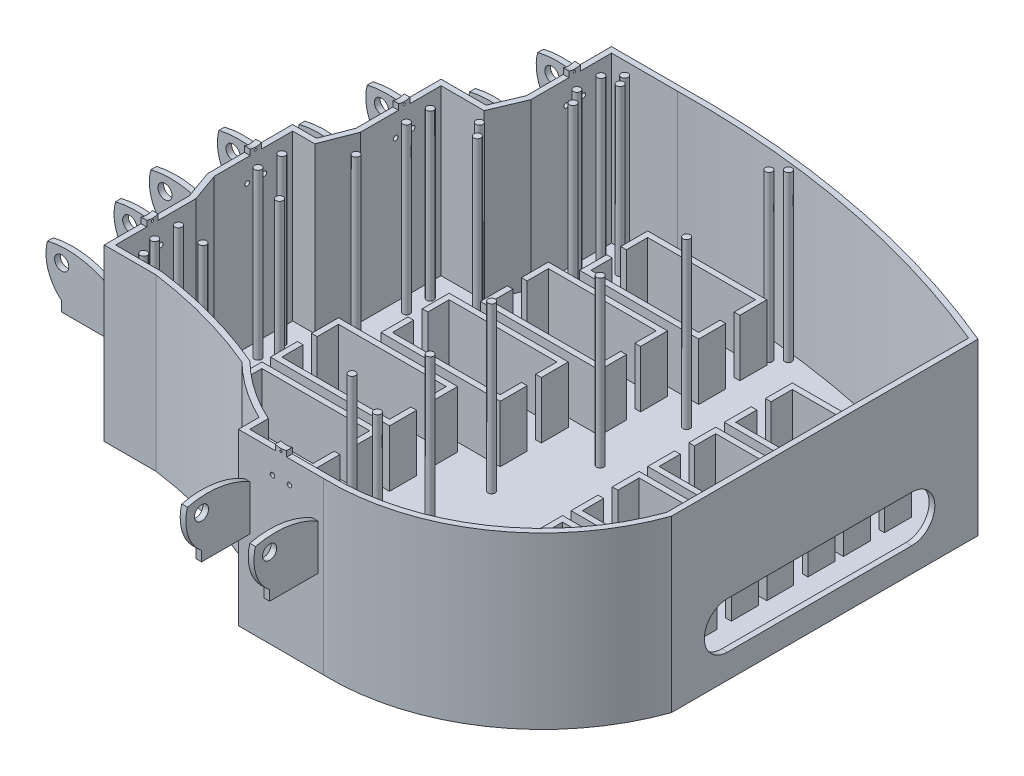
SolidWorks part; units mm, degrees
ref_plane "Front Plane" through (0, 0, 0) normal (0, 0, 1) x (1, 0, 0)
ref_plane "Top Plane" through (0, 0, 0) normal (0, 1, 0) x (1, 0, 0)
ref_plane "Right Plane" through (0, 0, 0) normal (1, 0, 0) x (0, 0, -1)
ref_plane "Palm Side Plane" through (0, 38.1, 0) normal (0, 1, 0) x (1, 0, 0)
ref_plane "Left Side Plane" through (0, 0, 63.5) normal (0, 0, 1) x (1, 0, 0)
ref_plane "Top Side Plane" through (-69.85, 0, 0) normal (1, 0, 0) x (0, 0, -1)
ref_plane "Wrist Plane" through (62.9138, 0, 0) normal (1, 0, 0) x (0, 0, -1)
sketch "Hand Direction Arrow" plane through (0, 38.1, 0) normal (0, 1, 0) x (1, 0, 0)
  line L0 (49.8191, -114.0829) -> (-36.738, -114.0829) construction
  line L1 (-36.738, -114.0829) -> (-22.4792, -131.555) construction
  line L2 (-36.738, -114.0829) -> (-22.4792, -99.8241) construction
sketch "Sketch2" plane through (0, 0, 0) normal (0, 1, 0) x (1, 0, 0)
  line L5 (-69.85, -63.5) -> (69.85, 63.5) construction
  line L6 (-69.85, 63.5) -> (69.85, -63.5) construction
  line L7 (-20.7784, 52.7587) -> (-36.189, 52.7587)
  line L8 (-36.189, 52.7587) -> (-36.189, 33.7087)
  line L9 (-42.9594, -42.4913) -> (-54.5039, -42.4913)
  line L10 (-54.5039, -42.4913) -> (-54.5039, -23.4413)
  line L11 (-54.5039, -23.4413) -> (-56.7676, -17.0913)
  line L12 (-51.4171, 1.9587) -> (-48.9477, 8.3087)
  line L14 (-56.7676, -17.0913) -> (-56.7676, 1.9587)
  line L15 (-56.7676, 1.9587) -> (-51.4171, 1.9587)
  line L16 (-38.8642, 27.3587) -> (-36.189, 33.7087)
  line L19 (15.3118, -63.2103) -> (-3.7382, -63.2103)
  line L20 (-3.7382, -63.2103) -> (-3.7382, -58.593)
  line L21 (61.5724, -31.5884) -> (61.5724, 37.0553)
  line L22 (-48.9477, 8.3087) -> (-48.9477, 27.3587)
  line L23 (-48.9477, 27.3587) -> (-38.8642, 27.3587)
  arc A0 (61.5724, 37.0553) -> (-20.7784, 52.7587) centre (-16.6219, -149.2259) ccw
  arc A2 (-42.9594, -42.4913) -> (-16.4221, -49.7553) centre (-56.8306, -145.2734) cw
  arc A3 (15.3118, -63.2103) -> (61.5724, -31.5884) centre (16.7508, -15.6666) ccw
  arc A5 (-3.7382, -58.593) -> (-16.4221, -49.7553) centre (16.7508, -15.6666) cw
  point P0 (0, 0)
  dimension "D1" = 19.05
  dimension "D2" = 19.05
  dimension "D3" = 19.05
  dimension "D4" = 19.05
  dimension "D5" = 19.05
  dimension "D6" = 6.35
  dimension "D7" = 6.35
extrude "Boss-Extrude1" add sketch "Sketch2" along normal blind 38.1
sketch "Sketch3" plane through (0, 38.1, 0) normal (0, 1, 0) x (1, 0, 0)
  line L5 (-68.58, -62.23) -> (68.58, 62.23) construction
  line L6 (-68.58, 62.23) -> (68.58, -62.23) construction
  line L7 (-20.1932, 51.4997) -> (-34.919, 51.4997)
  line L8 (-34.919, 51.4997) -> (-34.919, 33.4521)
  line L10 (-36.189, 52.7587) -> (-36.189, 33.7087) construction
  line L11 (-54.5039, -23.4413) -> (-54.5039, -42.4913) construction
  line L12 (-42.8744, -41.2213) -> (-53.2339, -41.2213)
  line L13 (-53.2339, -41.2213) -> (-53.2339, -23.2217)
  line L18 (-55.4976, -16.8717) -> (-55.4976, 0.6887)
  line L19 (-55.4976, 0.6887) -> (-50.5484, 0.6887)
  line L22 (-56.7676, 1.9587) -> (-56.7676, -17.0913) construction
  line L23 (-51.4171, 1.9587) -> (-56.7676, 1.9587) construction
  line L24 (-47.6777, 8.0704) -> (-47.6777, 26.0887)
  line L25 (-47.6777, 26.0887) -> (-38.0211, 26.0887)
  line L26 (-48.9477, 27.3587) -> (-48.9477, 8.3087) construction
  line L27 (-38.8642, 27.3587) -> (-48.9477, 27.3587) construction
  line L28 (-38.0211, 26.0887) -> (-34.919, 33.4521)
  line L29 (-36.189, 33.7087) -> (-38.8642, 27.3587) construction
  line L30 (-50.5484, 0.6887) -> (-47.6777, 8.0704)
  line L31 (-54.5039, -42.4913) -> (-42.9594, -42.4913) construction
  line L32 (-53.2339, -23.2217) -> (-55.4976, -16.8717)
  line L33 (-56.7676, -17.0913) -> (-54.5039, -23.4413) construction
  line L34 (-48.9477, 8.3087) -> (-51.4171, 1.9587) construction
  line L35 (15.3312, -61.9403) -> (-2.4682, -61.9403)
  line L36 (-2.4682, -61.9403) -> (-2.4682, -57.7843)
  line L37 (-3.7382, -58.593) -> (-3.7382, -63.2103) construction
  line L38 (-3.7382, -63.2103) -> (15.3118, -63.2103) construction
  line L39 (60.3024, -31.368) -> (60.3024, 36.2091)
  line L40 (61.5724, -31.5884) -> (61.5724, 37.0553) construction
  arc A1 (-20.1932, 51.4997) -> (60.3024, 36.2091) centre (-16.6219, -149.2259) cw
  arc A4 (61.5724, 37.0553) -> (-20.7784, 52.7587) centre (-16.6219, -149.2259) ccw construction
  arc A6 (-15.7053, -48.6798) -> (-2.4682, -57.7843) centre (16.7508, -15.6666) ccw
  arc A7 (15.3118, -63.2103) -> (61.5724, -31.5884) centre (16.7508, -15.6666) ccw construction
  arc A8 (-42.8744, -41.2213) -> (-15.7053, -48.6798) centre (-56.8306, -145.2734) cw
  arc A9 (-16.4221, -49.7553) -> (-42.9594, -42.4913) centre (-56.8306, -145.2734) ccw construction
  arc A11 (15.3118, -63.2103) -> (61.5724, -31.5884) centre (16.7508, -15.6666) ccw construction
  arc A12 (15.3312, -61.9403) -> (60.3024, -31.368) centre (16.7508, -15.6666) ccw
  point P0 (0, 0)
  point P6 (-45.5127, -25.7954)
  point P29 (-45.5127, -25.7954)
  point P52 (-54.0923, 1.9587)
  dimension "D2" = 1.27
  dimension "D3" = 1.27
  dimension "D5" = 1.27
  dimension "D6" = 1.27
  dimension "D8" = 1.27
  dimension "D4" = 1.27
  dimension "D7" = 1.27
  dimension "D9" = 1.27
  dimension "D10" = 1.27
  dimension "D11" = 1.27
  dimension "D12" = 1.27
  dimension "D13" = 1.27
  dimension "D14" = 1.27
  dimension "D15" = 1.27
  dimension "D16" = 1.27
  dimension "D17" = 1.27
extrude "Cut-Extrude1" cut sketch "Sketch3" against normal blind 36.83
sketch "Sketch6" plane through (0, 0, 0) normal (0, 1, 0) x (1, 0, 0)
  line L0 (-38.2959, -32.597) -> (-37.0259, -32.597)
  line L5 (-63.3937, -68.1577) -> (73.7663, 56.3023) construction
  line L6 (-64.5742, 57.9506) -> (72.5858, -66.5094) construction
  line L7 (-12.8959, -37.3595) -> (-37.0259, -37.3595)
  line L8 (-12.8959, -37.3595) -> (-12.8959, -32.597)
  line L9 (-12.8959, -24.6595) -> (-37.0259, -24.6595)
  line L10 (-37.0259, -37.3595) -> (-37.0259, -32.597)
  line L11 (-12.8959, -37.3595) -> (-37.0259, -24.6595) construction
  line L12 (-12.8959, -24.6595) -> (-37.0259, -37.3595) construction
  line L13 (-11.6259, -38.6295) -> (-38.2959, -38.6295)
  line L14 (-11.6259, -38.6295) -> (-11.6259, -32.597)
  line L15 (-11.6259, -23.3895) -> (-38.2959, -23.3895)
  line L16 (-38.2959, -38.6295) -> (-38.2959, -32.597)
  line L17 (-11.6259, -38.6295) -> (-38.2959, -23.3895) construction
  line L18 (-11.6259, -23.3895) -> (-38.2959, -38.6295) construction
  line L19 (-38.2959, -29.422) -> (-37.0259, -29.422)
  line L20 (-38.2959, -29.422) -> (-38.2959, -23.3895)
  line L21 (-37.0259, -29.422) -> (-37.0259, -24.6595)
  line L22 (-12.8959, -32.597) -> (-11.6259, -32.597)
  line L23 (-12.8959, -29.422) -> (-11.6259, -29.422)
  line L24 (-12.8959, -29.422) -> (-12.8959, -24.6595)
  line L25 (-11.6259, -29.422) -> (-11.6259, -23.3895)
  point P0 (5.5042, -5.6391)
  point P6 (-24.9609, -31.0095)
  point P29 (-24.9609, -31.0095)
  dimension "D6" = 1.27
  dimension "D7" = 1.27
  dimension "D9" = 12.7
  dimension "D10" = 24.13
  dimension "D11" = 4.7625
  dimension "D12" = 4.7625
  dimension "D13" = 4.7625
  dimension "D14" = 4.7625
extrude "Boss-Extrude2" add sketch "Sketch6" along normal blind 13.97
sketch "Sketch7" plane through (0, 0, 0) normal (0, 1, 0) x (1, 0, 0)
  line L0 (-38.2959, -15.452) -> (-37.0259, -15.452)
  line L5 (-11.6259, -23.3895) -> (-38.2959, -23.3895) construction
  line L6 (-38.2959, -23.3895) -> (-38.2959, -29.422) construction
  line L7 (-12.8959, -20.2145) -> (-37.0259, -20.2145)
  line L8 (-12.8959, -20.2145) -> (-12.8959, -15.452)
  line L9 (-12.8959, -7.5145) -> (-37.0259, -7.5145)
  line L10 (-37.0259, -20.2145) -> (-37.0259, -15.452)
  line L11 (-12.8959, -20.2145) -> (-37.0259, -7.5145) construction
  line L12 (-12.8959, -7.5145) -> (-37.0259, -20.2145) construction
  line L13 (-11.6259, -21.4845) -> (-38.2959, -21.4845)
  line L14 (-11.6259, -21.4845) -> (-11.6259, -15.452)
  line L15 (-11.6259, -6.2445) -> (-38.2959, -6.2445)
  line L16 (-38.2959, -21.4845) -> (-38.2959, -15.452)
  line L17 (-11.6259, -21.4845) -> (-38.2959, -6.2445) construction
  line L18 (-11.6259, -6.2445) -> (-38.2959, -21.4845) construction
  line L19 (-38.2959, -12.277) -> (-37.0259, -12.277)
  line L20 (-38.2959, -12.277) -> (-38.2959, -6.2445)
  line L21 (-37.0259, -12.277) -> (-37.0259, -7.5145)
  line L22 (-12.8959, -15.452) -> (-11.6259, -15.452)
  line L23 (-12.8959, -12.277) -> (-11.6259, -12.277)
  line L24 (-12.8959, -12.277) -> (-12.8959, -7.5145)
  line L25 (-11.6259, -12.277) -> (-11.6259, -6.2445)
  point P0 (-14.8998, -5.4903)
  point P6 (-24.9609, -13.8645)
  point P29 (-24.9609, -13.8645)
  dimension "D2" = 1.905
  dimension "D3" = 0
  dimension "D6" = 1.27
  dimension "D7" = 1.27
  dimension "D9" = 12.7
  dimension "D10" = 24.13
  dimension "D11" = 4.7625
  dimension "D12" = 4.7625
  dimension "D13" = 4.7625
  dimension "D14" = 4.7625
extrude "Boss-Extrude3" add sketch "Sketch7" along normal blind 13.97
sketch "Sketch15" plane through (0, 0, 0) normal (0, -1, 0) x (1, 0, 0)
  line L0 (-30.6759, -4.868) -> (-29.4059, -4.868)
  line L5 (-11.6259, 6.2445) -> (-38.2959, 6.2445) construction
  line L6 (-38.2959, 6.2445) -> (-38.2959, 12.277) construction
  line L7 (-5.2759, -9.6305) -> (-29.4059, -9.6305)
  line L8 (-5.2759, -9.6305) -> (-5.2759, -4.868)
  line L9 (-5.2759, 3.0695) -> (-29.4059, 3.0695)
  line L10 (-29.4059, -9.6305) -> (-29.4059, -4.868)
  line L11 (-5.2759, -9.6305) -> (-29.4059, 3.0695) construction
  line L12 (-5.2759, 3.0695) -> (-29.4059, -9.6305) construction
  line L13 (-4.0059, -10.9005) -> (-30.6759, -10.9005)
  line L14 (-4.0059, -10.9005) -> (-4.0059, -4.868)
  line L15 (-4.0059, 4.3395) -> (-30.6759, 4.3395)
  line L16 (-30.6759, -10.9005) -> (-30.6759, -4.868)
  line L17 (-4.0059, -10.9005) -> (-30.6759, 4.3395) construction
  line L18 (-4.0059, 4.3395) -> (-30.6759, -10.9005) construction
  line L19 (-30.6759, -1.693) -> (-29.4059, -1.693)
  line L20 (-30.6759, -1.693) -> (-30.6759, 4.3395)
  line L21 (-29.4059, -1.693) -> (-29.4059, 3.0695)
  line L22 (-5.2759, -4.868) -> (-4.0059, -4.868)
  line L23 (-5.2759, -1.693) -> (-4.0059, -1.693)
  line L24 (-5.2759, -1.693) -> (-5.2759, 3.0695)
  line L25 (-4.0059, -1.693) -> (-4.0059, 4.3395)
  point P0 (-6.5637, 8.998)
  point P6 (-17.3409, -3.2805)
  point P29 (-17.3409, -3.2805)
  dimension "D2" = 1.905
  dimension "D3" = 7.62
  dimension "D6" = 1.27
  dimension "D7" = 1.27
  dimension "D9" = 12.7
  dimension "D10" = 24.13
  dimension "D11" = 4.7625
  dimension "D12" = 4.7625
  dimension "D13" = 4.7625
  dimension "D14" = 4.7625
extrude "Boss-Extrude4" add sketch "Sketch15" against normal blind 13.97
sketch "Sketch16" plane through (0, 0, 0) normal (0, -1, 0) x (1, 0, 0)
  line L0 (-25.5959, -22.013) -> (-24.3259, -22.013)
  line L5 (-30.6759, -10.9005) -> (-4.0059, -10.9005) construction
  line L6 (-30.6759, -4.868) -> (-30.6759, -10.9005) construction
  line L7 (-0.1959, -26.7755) -> (-24.3259, -26.7755)
  line L8 (-0.1959, -26.7755) -> (-0.1959, -22.013)
  line L9 (-0.1959, -14.0755) -> (-24.3259, -14.0755)
  line L10 (-24.3259, -26.7755) -> (-24.3259, -22.013)
  line L11 (-0.1959, -26.7755) -> (-24.3259, -14.0755) construction
  line L12 (-0.1959, -14.0755) -> (-24.3259, -26.7755) construction
  line L13 (1.0741, -28.0455) -> (-25.5959, -28.0455)
  line L14 (1.0741, -28.0455) -> (1.0741, -22.013)
  line L15 (1.0741, -12.8055) -> (-25.5959, -12.8055)
  line L16 (-25.5959, -28.0455) -> (-25.5959, -22.013)
  line L17 (1.0741, -28.0455) -> (-25.5959, -12.8055) construction
  line L18 (1.0741, -12.8055) -> (-25.5959, -28.0455) construction
  line L19 (-25.5959, -18.838) -> (-24.3259, -18.838)
  line L20 (-25.5959, -18.838) -> (-25.5959, -12.8055)
  line L21 (-24.3259, -18.838) -> (-24.3259, -14.0755)
  line L22 (-0.1959, -22.013) -> (1.0741, -22.013)
  line L23 (-0.1959, -18.838) -> (1.0741, -18.838)
  line L24 (-0.1959, -18.838) -> (-0.1959, -14.0755)
  line L25 (1.0741, -18.838) -> (1.0741, -12.8055)
  point P0 (1.9027, -6.9539)
  point P6 (-12.2609, -20.4255)
  point P29 (-12.2609, -20.4255)
  dimension "D2" = 1.905
  dimension "D3" = 5.08
  dimension "D6" = 1.27
  dimension "D7" = 1.27
  dimension "D9" = 12.7
  dimension "D10" = 24.13
  dimension "D11" = 4.7625
  dimension "D12" = 4.7625
  dimension "D13" = 4.7625
  dimension "D14" = 4.7625
extrude "Boss-Extrude5" add sketch "Sketch16" against normal blind 13.97
sketch "Sketch17" plane through (0, 0, 0) normal (0, -1, 0) x (1, 0, 0)
  line L0 (-20.5159, -39.158) -> (-19.2459, -39.158)
  line L5 (-25.5959, -28.0455) -> (1.0741, -28.0455) construction
  line L6 (-25.5959, -22.013) -> (-25.5959, -28.0455) construction
  line L7 (4.8841, -43.9205) -> (-19.2459, -43.9205)
  line L8 (4.8841, -43.9205) -> (4.8841, -39.158)
  line L9 (4.8841, -31.2205) -> (-19.2459, -31.2205)
  line L10 (-19.2459, -43.9205) -> (-19.2459, -39.158)
  line L11 (4.8841, -43.9205) -> (-19.2459, -31.2205) construction
  line L12 (4.8841, -31.2205) -> (-19.2459, -43.9205) construction
  line L13 (6.1541, -45.1905) -> (-20.5159, -45.1905)
  line L14 (6.1541, -45.1905) -> (6.1541, -39.158)
  line L15 (6.1541, -29.9505) -> (-20.5159, -29.9505)
  line L16 (-20.5159, -45.1905) -> (-20.5159, -39.158)
  line L17 (6.1541, -45.1905) -> (-20.5159, -29.9505) construction
  line L18 (6.1541, -29.9505) -> (-20.5159, -45.1905) construction
  line L19 (-20.5159, -35.983) -> (-19.2459, -35.983)
  line L20 (-20.5159, -35.983) -> (-20.5159, -29.9505)
  line L21 (-19.2459, -35.983) -> (-19.2459, -31.2205)
  line L22 (4.8841, -39.158) -> (6.1541, -39.158)
  line L23 (4.8841, -35.983) -> (6.1541, -35.983)
  line L24 (4.8841, -35.983) -> (4.8841, -31.2205)
  line L25 (6.1541, -35.983) -> (6.1541, -29.9505)
  point P0 (6.1079, -24.4951)
  point P6 (-7.1809, -37.5705)
  point P29 (-7.1809, -37.5705)
  dimension "D2" = 1.905
  dimension "D3" = 5.08
  dimension "D6" = 1.27
  dimension "D7" = 1.27
  dimension "D9" = 12.7
  dimension "D10" = 24.13
  dimension "D11" = 4.7625
  dimension "D12" = 4.7625
  dimension "D13" = 4.7625
  dimension "D14" = 4.7625
extrude "Boss-Extrude6" add sketch "Sketch17" against normal blind 13.97
sketch "Sketch18" plane through (0, 0, 0) normal (0, -1, 0) x (1, 0, 0)
  line L0 (14.981, 42.6949) -> (16.251, 42.6949)
  line L7 (40.381, 37.9324) -> (16.251, 37.9324)
  line L8 (40.381, 37.9324) -> (40.381, 42.6949)
  line L9 (40.381, 50.6324) -> (16.251, 50.6324)
  line L10 (16.251, 37.9324) -> (16.251, 42.6949)
  line L11 (40.381, 37.9324) -> (16.251, 50.6324) construction
  line L12 (40.381, 50.6324) -> (16.251, 37.9324) construction
  line L13 (41.651, 36.6624) -> (14.981, 36.6624)
  line L14 (41.651, 36.6624) -> (41.651, 42.6949)
  line L15 (41.651, 51.9024) -> (14.981, 51.9024)
  line L16 (14.981, 36.6624) -> (14.981, 42.6949)
  line L17 (41.651, 36.6624) -> (14.981, 51.9024) construction
  line L18 (41.651, 51.9024) -> (14.981, 36.6624) construction
  line L19 (14.981, 45.8699) -> (16.251, 45.8699)
  line L20 (14.981, 45.8699) -> (14.981, 51.9024)
  line L21 (16.251, 45.8699) -> (16.251, 50.6324)
  line L22 (40.381, 42.6949) -> (41.651, 42.6949)
  line L23 (40.381, 45.8699) -> (41.651, 45.8699)
  line L24 (40.381, 45.8699) -> (40.381, 50.6324)
  line L25 (41.651, 45.8699) -> (41.651, 51.9024)
  point P0 (43.5107, 54.1626)
  point P6 (28.316, 44.2824)
  point P29 (28.316, 44.2824)
  dimension "D6" = 1.27
  dimension "D7" = 1.27
  dimension "D9" = 12.7
  dimension "D10" = 24.13
  dimension "D11" = 4.7625
  dimension "D12" = 4.7625
  dimension "D13" = 4.7625
  dimension "D14" = 4.7625
extrude "Boss-Extrude7" add sketch "Sketch18" against normal blind 13.97
sketch "Sketch19" plane through (0, 0, 0) normal (0, -1, 0) x (1, 0, 0)
  line L0 (25.141, 25.5499) -> (26.411, 25.5499)
  line L5 (14.981, 36.6624) -> (41.651, 36.6624) construction
  line L6 (14.981, 42.6949) -> (14.981, 36.6624) construction
  line L7 (50.541, 20.7874) -> (26.411, 20.7874)
  line L8 (50.541, 20.7874) -> (50.541, 25.5499)
  line L9 (50.541, 33.4874) -> (26.411, 33.4874)
  line L10 (26.411, 20.7874) -> (26.411, 25.5499)
  line L11 (50.541, 20.7874) -> (26.411, 33.4874) construction
  line L12 (50.541, 33.4874) -> (26.411, 20.7874) construction
  line L13 (51.811, 19.5174) -> (25.141, 19.5174)
  line L14 (51.811, 19.5174) -> (51.811, 25.5499)
  line L15 (51.811, 34.7574) -> (25.141, 34.7574)
  line L16 (25.141, 19.5174) -> (25.141, 25.5499)
  line L17 (51.811, 19.5174) -> (25.141, 34.7574) construction
  line L18 (51.811, 34.7574) -> (25.141, 19.5174) construction
  line L19 (25.141, 28.7249) -> (26.411, 28.7249)
  line L20 (25.141, 28.7249) -> (25.141, 34.7574)
  line L21 (26.411, 28.7249) -> (26.411, 33.4874)
  line L22 (50.541, 25.5499) -> (51.811, 25.5499)
  line L23 (50.541, 28.7249) -> (51.811, 28.7249)
  line L24 (50.541, 28.7249) -> (50.541, 33.4874)
  line L25 (51.811, 28.7249) -> (51.811, 34.7574)
  point P0 (52.4146, 37.8023)
  point P6 (38.476, 27.1374)
  point P29 (38.476, 27.1374)
  dimension "D2" = 1.905
  dimension "D3" = 10.16
  dimension "D6" = 1.27
  dimension "D7" = 1.27
  dimension "D9" = 12.7
  dimension "D10" = 24.13
  dimension "D11" = 4.7625
  dimension "D12" = 4.7625
  dimension "D13" = 4.7625
  dimension "D14" = 4.7625
extrude "Boss-Extrude8" add sketch "Sketch19" against normal blind 13.97
sketch "Sketch20" plane through (0, 0, 0) normal (0, -1, 0) x (1, 0, 0)
  line L0 (25.141, 8.4049) -> (26.411, 8.4049)
  line L5 (25.141, 25.5499) -> (25.141, 19.5174) construction
  line L6 (25.141, 19.5174) -> (51.811, 19.5174) construction
  line L7 (50.541, 3.6424) -> (26.411, 3.6424)
  line L8 (50.541, 3.6424) -> (50.541, 8.4049)
  line L9 (50.541, 16.3424) -> (26.411, 16.3424)
  line L10 (26.411, 3.6424) -> (26.411, 8.4049)
  line L11 (50.541, 3.6424) -> (26.411, 16.3424) construction
  line L12 (50.541, 16.3424) -> (26.411, 3.6424) construction
  line L13 (51.811, 2.3724) -> (25.141, 2.3724)
  line L14 (51.811, 2.3724) -> (51.811, 8.4049)
  line L15 (51.811, 17.6124) -> (25.141, 17.6124)
  line L16 (25.141, 2.3724) -> (25.141, 8.4049)
  line L17 (51.811, 2.3724) -> (25.141, 17.6124) construction
  line L18 (51.811, 17.6124) -> (25.141, 2.3724) construction
  line L19 (25.141, 11.5799) -> (26.411, 11.5799)
  line L20 (25.141, 11.5799) -> (25.141, 17.6124)
  line L21 (26.411, 11.5799) -> (26.411, 16.3424)
  line L22 (50.541, 8.4049) -> (51.811, 8.4049)
  line L23 (50.541, 11.5799) -> (51.811, 11.5799)
  line L24 (50.541, 11.5799) -> (50.541, 16.3424)
  line L25 (51.811, 11.5799) -> (51.811, 17.6124)
  point P0 (54.8865, 20.8211)
  point P6 (38.476, 9.9924)
  point P29 (38.476, 9.9924)
  dimension "D2" = 0
  dimension "D3" = 1.905
  dimension "D6" = 1.27
  dimension "D7" = 1.27
  dimension "D9" = 12.7
  dimension "D10" = 24.13
  dimension "D11" = 4.7625
  dimension "D12" = 4.7625
  dimension "D13" = 4.7625
  dimension "D14" = 4.7625
extrude "Boss-Extrude9" add sketch "Sketch20" against normal blind 13.97
sketch "Sketch21" plane through (0, 0, 0) normal (0, -1, 0) x (1, 0, 0)
  line L0 (25.141, -8.7401) -> (26.411, -8.7401)
  line L5 (25.141, 2.3724) -> (51.811, 2.3724) construction
  line L6 (25.141, 8.4049) -> (25.141, 2.3724) construction
  line L7 (50.541, -13.5026) -> (26.411, -13.5026)
  line L8 (50.541, -13.5026) -> (50.541, -8.7401)
  line L9 (50.541, -0.8026) -> (26.411, -0.8026)
  line L10 (26.411, -13.5026) -> (26.411, -8.7401)
  line L11 (50.541, -13.5026) -> (26.411, -0.8026) construction
  line L12 (50.541, -0.8026) -> (26.411, -13.5026) construction
  line L13 (51.811, -14.7726) -> (25.141, -14.7726)
  line L14 (51.811, -14.7726) -> (51.811, -8.7401)
  line L15 (51.811, 0.4674) -> (25.141, 0.4674)
  line L16 (25.141, -14.7726) -> (25.141, -8.7401)
  line L17 (51.811, -14.7726) -> (25.141, 0.4674) construction
  line L18 (51.811, 0.4674) -> (25.141, -14.7726) construction
  line L19 (25.141, -5.5651) -> (26.411, -5.5651)
  line L20 (25.141, -5.5651) -> (25.141, 0.4674)
  line L21 (26.411, -5.5651) -> (26.411, -0.8026)
  line L22 (50.541, -8.7401) -> (51.811, -8.7401)
  line L23 (50.541, -5.5651) -> (51.811, -5.5651)
  line L24 (50.541, -5.5651) -> (50.541, -0.8026)
  line L25 (51.811, -5.5651) -> (51.811, 0.4674)
  point P0 (52.1156, 3.8173)
  point P6 (38.476, -7.1526)
  point P29 (38.476, -7.1526)
  dimension "D2" = 1.905
  dimension "D3" = 0
  dimension "D6" = 1.27
  dimension "D7" = 1.27
  dimension "D9" = 12.7
  dimension "D10" = 24.13
  dimension "D11" = 4.7625
  dimension "D12" = 4.7625
  dimension "D13" = 4.7625
  dimension "D14" = 4.7625
extrude "Boss-Extrude10" add sketch "Sketch21" against normal blind 13.97
sketch "Sketch22" plane through (0, 0, 0) normal (0, -1, 0) x (1, 0, 0)
  line L0 (25.141, -25.8851) -> (26.411, -25.8851)
  line L5 (25.141, -14.7726) -> (51.811, -14.7726) construction
  line L6 (25.141, -8.7401) -> (25.141, -14.7726) construction
  line L7 (50.541, -30.6476) -> (26.411, -30.6476)
  line L8 (50.541, -30.6476) -> (50.541, -25.8851)
  line L9 (50.541, -17.9476) -> (26.411, -17.9476)
  line L10 (26.411, -30.6476) -> (26.411, -25.8851)
  line L11 (50.541, -30.6476) -> (26.411, -17.9476) construction
  line L12 (50.541, -17.9476) -> (26.411, -30.6476) construction
  line L13 (51.811, -31.9176) -> (25.141, -31.9176)
  line L14 (51.811, -31.9176) -> (51.811, -25.8851)
  line L15 (51.811, -16.6776) -> (25.141, -16.6776)
  line L16 (25.141, -31.9176) -> (25.141, -25.8851)
  line L17 (51.811, -31.9176) -> (25.141, -16.6776) construction
  line L18 (51.811, -16.6776) -> (25.141, -31.9176) construction
  line L19 (25.141, -22.7101) -> (26.411, -22.7101)
  line L20 (25.141, -22.7101) -> (25.141, -16.6776)
  line L21 (26.411, -22.7101) -> (26.411, -17.9476)
  line L22 (50.541, -25.8851) -> (51.811, -25.8851)
  line L23 (50.541, -22.7101) -> (51.811, -22.7101)
  line L24 (50.541, -22.7101) -> (50.541, -17.9476)
  line L25 (51.811, -22.7101) -> (51.811, -16.6776)
  point P0 (57.6091, -14.277)
  point P6 (38.476, -24.2976)
  point P29 (38.476, -24.2976)
  dimension "D2" = 1.905
  dimension "D3" = 0
  dimension "D6" = 1.27
  dimension "D7" = 1.27
  dimension "D9" = 12.7
  dimension "D10" = 24.13
  dimension "D11" = 4.7625
  dimension "D12" = 4.7625
  dimension "D13" = 4.7625
  dimension "D14" = 4.7625
extrude "Boss-Extrude11" add sketch "Sketch22" against normal blind 13.97
sketch "Sketch25" plane through (0, 0, 63.5) normal (0, 0, 1) x (1, 0, 0)
  line L1 (49.8191, 38.1) -> (-36.738, 38.1) construction
  line L6 (-3.7382, 38.1) -> (-3.7382, 0) construction
  line L7 (15.3118, 38.1) -> (15.3118, 0) construction
  circle A0 centre (7.6918, 33.02) radius 0.508
  circle A1 centre (3.8818, 33.02) radius 0.508
  dimension "D3" = 7.62
  dimension "D1" = 5.08
  dimension "D2" = 5.08
  dimension "D4" = 7.62
extrude "Thumb Holes" cut sketch "Sketch25" against normal blind 12.7
sketch "Sketch31" plane through (-69.85, 0, 0) normal (1, 0, 0) x (0, 0, -1)
  line L0 (-23.4413, 38.1) -> (-23.4413, 0) construction
  line L1 (-23.4413, 38.1) -> (-42.4913, 38.1) construction
  line L2 (-42.4913, 38.1) -> (-42.4913, 0) construction
  circle A0 centre (-31.0613, 33.02) radius 0.508
  circle A1 centre (-34.8713, 33.02) radius 0.508
  dimension "D1" = 7.62
  dimension "D2" = 5.08
  dimension "D3" = 5.08
  dimension "D4" = 7.62
extrude "Index Finger Holes" cut sketch "Sketch31" along normal blind 17.018
sketch "Sketch32" plane through (-69.85, 0, 0) normal (1, 0, 0) x (0, 0, -1)
  line L0 (1.9587, 38.1) -> (1.9587, 0) construction
  line L1 (-17.0913, 38.1) -> (-17.0913, 0) construction
  line L2 (1.9587, 38.1) -> (-17.0913, 38.1) construction
  circle A0 centre (-9.4713, 33.02) radius 0.508
  circle A1 centre (-5.6613, 33.02) radius 0.508
  dimension "D1" = 7.62
  dimension "D2" = 7.62
  dimension "D3" = 5.08
  dimension "D4" = 5.08
extrude "Middle Finger Holes" cut sketch "Sketch32" along normal blind 15.24
sketch "Sketch33" plane through (-69.85, 0, 0) normal (1, 0, 0) x (0, 0, -1)
  line L0 (27.3587, 38.1) -> (27.3587, 0) construction
  line L1 (27.3587, 38.1) -> (8.3087, 38.1) construction
  line L2 (8.3087, 38.1) -> (8.3087, 0) construction
  circle A0 centre (15.9287, 33.02) radius 0.508
  circle A1 centre (19.7387, 33.02) radius 0.508
  dimension "D1" = 7.62
  dimension "D2" = 5.08
  dimension "D3" = 5.08
  dimension "D4" = 7.62
extrude "Ring Finger Holes" cut sketch "Sketch33" along normal blind 22.86
sketch "Sketch34" plane through (-69.85, 0, 0) normal (1, 0, 0) x (0, 0, -1)
  line L0 (52.7587, 38.1) -> (33.7087, 38.1) construction
  line L1 (52.8014, 0) -> (52.8014, 38.1) construction
  line L2 (33.7087, 38.1) -> (33.7087, 0) construction
  circle A0 centre (41.3287, 33.02) radius 0.508
  circle A1 centre (45.1814, 33.02) radius 0.508
  dimension "D1" = 5.08
  dimension "D2" = 7.62
  dimension "D3" = 7.62
  dimension "D4" = 5.08
extrude "Pinky Finger Holes" cut sketch "Sketch34" along normal blind 35.56
sketch "Sketch26" plane through (0, 38.1, 0) normal (0, 1, 0) x (1, 0, 0)
  line L0 (-1.8504, -40.4696) -> (-48.4714, -40.4696) construction
  line L1 (8.3049, 24.2976) -> (8.3049, 48.6758) construction
  line L2 (6.0975, 7.1526) -> (6.0975, 46.5196) construction
  line L3 (-1.0566, -9.9924) -> (-1.0566, -39.6758) construction
  line L4 (-53.2339, -23.2217) -> (-53.2339, -41.2213) construction
  line L5 (-37.0259, -15.452) -> (-38.2959, -15.452) construction
  line L6 (14.981, -45.8699) -> (16.251, -45.8699) construction
  line L7 (25.141, -28.7249) -> (26.411, -28.7249) construction
  line L8 (25.141, -11.5799) -> (26.411, -11.5799) construction
  line L9 (25.141, 5.5651) -> (26.411, 5.5651) construction
  line L10 (25.141, 22.7101) -> (26.411, 22.7101) construction
  line L11 (-30.6759, 1.693) -> (-29.4059, 1.693) construction
  line L12 (-25.5959, 18.838) -> (-24.3259, 18.838) construction
  line L13 (-20.5159, 35.983) -> (-19.2459, 35.983) construction
  line L14 (5.3037, 47.3134) -> (-28.0099, 47.3134) construction
  line L15 (7.5112, 49.4695) -> (-29.1533, 49.4695) construction
  line L16 (-53.2339, -23.2217) -> (-53.2339, -41.2213) construction
  line L17 (-55.4976, 0.6887) -> (-55.4976, -16.8717) construction
  line L18 (-47.6777, 26.0887) -> (-47.6777, 8.0704) construction
  line L19 (-47.6777, 26.0887) -> (-47.6777, 8.0704) construction
  line L20 (-34.919, 51.4997) -> (-34.919, 33.4521) construction
  line L21 (-34.919, 51.4997) -> (-34.919, 33.4521) construction
  line L22 (-37.0259, -32.597) -> (-38.2959, -32.597) construction
  line L23 (-49.2652, -39.6758) -> (-49.2652, -35.6333) construction
  circle A0 centre (8.4538, -44.2824) radius 0.7937
  circle A1 centre (3.1198, -27.1374) radius 0.7937
  circle A2 centre (-0.2629, -9.9924) radius 0.7937
  circle A3 centre (6.8912, 7.1526) radius 0.7938
  circle A4 centre (9.0987, 24.2976) radius 0.7937
  circle A5 centre (-1.8504, -39.6758) radius 0.7938
  circle A6 centre (7.5112, 48.6758) radius 0.7938
  circle A7 centre (5.3037, 46.5196) radius 0.7938
  circle A8 centre (-48.4714, -39.6758) radius 0.7937
  circle A9 centre (-52.3226, -10.2333) radius 0.7937
  circle A10 centre (-52.3226, -4.8993) radius 0.7937
  circle A11 centre (-43.8931, -13.8645) radius 0.7937
  circle A12 centre (-43.8931, 3.2805) radius 0.7937
  circle A13 centre (-33.8741, 20.4255) radius 0.7937
  circle A14 centre (-44.5027, 15.1667) radius 0.7937
  circle A15 centre (-29.6038, 37.5705) radius 0.7937
  circle A16 centre (-36.3066, 23.2954) radius 0.7937
  circle A17 centre (-44.5027, 20.5007) radius 0.7937
  circle A18 centre (-28.0099, 46.5196) radius 0.7937
  circle A19 centre (-29.1533, 48.6758) radius 0.7938
  circle A20 centre (-31.744, 40.5667) radius 0.7937
  circle A21 centre (-31.744, 45.9434) radius 0.7937
  circle A22 centre (-50.0589, -35.6333) radius 0.7937
  circle A23 centre (-50.0589, -30.2993) radius 0.7937
  circle A24 centre (-43.8931, -31.0095) radius 0.7937
  dimension "D6" = 0.254
  dimension "D7" = 0.254
  dimension "D14" = 1.5875
  dimension "D15" = 1.5875
  dimension "D16" = 1.5875
  dimension "D17" = 1.5875
  dimension "D18" = 1.5875
  dimension "D19" = 1.5875
  dimension "D20" = 1.5875
  dimension "D21" = 1.5875
  dimension "D22" = 1.5875
  dimension "D23" = 1.5875
  dimension "D24" = 1.5875
  dimension "D25" = 1.5875
  dimension "D26" = 1.5875
  dimension "D27" = 1.5875
  dimension "D28" = 1.5875
  dimension "D29" = 1.5875
  dimension "D30" = 1.5875
  dimension "D31" = 1.5875
  dimension "D32" = 1.5875
  dimension "D33" = 1.5875
  dimension "D34" = 1.5875
  dimension "D35" = 1.5875
  dimension "D41" = 0.254
  dimension "D52" = 1.5875
  dimension "D42" = 1.5875
  dimension "D53" = 1.5875
  dimension "D1" = 1.5875
  dimension "D2" = 1.5875
  dimension "D3" = 1.5875
  dimension "D4" = 1.5875
  dimension "D5" = 1.5875
  dimension "D8" = 1.5875
  dimension "D9" = 1.5875
  dimension "D10" = 1.5875
  dimension "D11" = 1.5875
  dimension "D12" = 0.254
  dimension "D13" = 0.254
  dimension "D36" = 0.254
  dimension "D37" = 0.254
  dimension "D38" = 0.254
  dimension "D39" = 0.254
  dimension "D40" = 0.254
  dimension "D43" = 3.175
  dimension "D44" = 3.175
  dimension "D45" = 3.175
  dimension "D46" = 3.175
  dimension "D47" = 3.175
  dimension "D48" = 3.175
  dimension "D49" = 3.175
  dimension "D50" = 3.175
  dimension "D51" = 1.5875
extrude "Guide Poles" add sketch "Sketch26" against normal blind 36.83
ref_plane "Pinky Attachment Plane" through (0, 0, -52.7587) normal (0, 0, -1) x (-1, 0, 0)
ref_plane "Ring Attachment Plane" through (0, 0, -27.3587) normal (0, 0, -1) x (-1, 0, 0)
ref_plane "Middle Attachment Plane" through (0, 0, -1.9587) normal (0, 0, -1) x (-1, 0, 0)
ref_plane "Pointer Attachment Plane" through (0, 0, 23.4413) normal (0, 0, -1) x (-1, 0, 0)
ref_plane "Thumb Attachment Plane" through (-3.7382, 0, 0) normal (-1, 0, 0) x (0, 0, 1)
sketch "Sketch35" plane through (0, 0, -52.7587) normal (0, 0, -1) x (-1, 0, 0)
  line L1 (36.189, 38.1) -> (36.189, 0) construction
  line L2 (38.8642, 38.1) -> (48.9477, 38.1) construction
  line L3 (36.189, 19.05) -> (40.634, 19.05)
  line L4 (40.634, 38.1) -> (40.634, 19.05) construction
  line L5 (36.189, 29.21) -> (36.189, 19.05)
  line L6 (36.189, 38.1) -> (36.189, 0) construction
  line L7 (40.634, 19.05) -> (46.984, 19.05)
  line L9 (46.984, 19.05) -> (46.984, 21.2492)
  circle A1 centre (46.984, 28.575) radius 1.5875
  arc A2 (50.159, 31.242) -> (46.984, 21.2492) centre (40.8478, 28.6996) cw
  arc A3 (50.159, 31.242) -> (36.189, 29.21) centre (45.7208, 12.7162) ccw
  dimension "D1" = 10.795
  dimension "D2" = 4.445
  dimension "D3" = 8.89
  dimension "D6" = 10.795
  dimension "D4" = 6.858
  dimension "D5" = 13.97
extrude "Pinky Attachment" add sketch "Sketch35" against normal blind 19.05
sketch "Sketch36" plane through (0, 0, -27.3587) normal (0, 0, -1) x (-1, 0, 0)
  line L0 (51.4171, 38.1) -> (56.7676, 38.1) construction
  line L3 (48.9477, 29.21) -> (48.9477, 19.05)
  line L4 (48.9477, 38.1) -> (48.9477, 0) construction
  line L5 (48.9477, 19.05) -> (53.3927, 19.05)
  line L6 (53.3927, 38.1) -> (53.3927, 19.05) construction
  line L7 (48.9477, 38.1) -> (48.9477, 0) construction
  line L8 (53.3927, 19.05) -> (59.7427, 19.05)
  line L9 (59.7427, 19.05) -> (59.7427, 21.2492)
  arc A0 (62.9177, 31.242) -> (59.7427, 21.2492) centre (53.6065, 28.6996) cw
  circle A1 centre (59.7427, 28.7074) radius 1.5875
  arc A2 (48.9477, 29.21) -> (62.9177, 31.242) centre (58.4796, 12.7162) cw
  dimension "D1" = 4.445
  dimension "D2" = 10.795
  dimension "D3" = 13.97
  dimension "D5" = 10.795
  dimension "D4" = 6.858
extrude "Ring Attachment" add sketch "Sketch36" against normal blind 19.05
sketch "Sketch37" plane through (0, 0, -1.9587) normal (0, 0, -1) x (-1, 0, 0)
  line L0 (51.4171, 38.1) -> (56.7676, 38.1) construction
  line L2 (56.7676, 29.21) -> (56.7676, 19.05)
  line L3 (56.7676, 38.1) -> (56.7676, 0) construction
  line L4 (56.7676, 19.05) -> (61.2126, 19.05)
  line L7 (61.2126, 38.1) -> (61.2126, 19.05) construction
  line L8 (61.2126, 19.05) -> (67.5626, 19.05)
  line L9 (67.5626, 19.05) -> (67.5626, 21.2492)
  arc A2 (70.7376, 31.242) -> (67.5626, 21.2492) centre (61.4264, 28.6996) cw
  circle A3 centre (67.5626, 28.575) radius 1.5875
  arc A4 (56.7676, 29.21) -> (70.7376, 31.242) centre (66.2994, 12.7162) cw
  dimension "D1" = 4.445
  dimension "D4" = 10.795
  dimension "D3" = 13.97
  dimension "D2" = 10.795
  dimension "D5" = 6.858
extrude "Middle Attachment" add sketch "Sketch37" against normal blind 19.05
sketch "Sketch38" plane through (0, 0, 23.4413) normal (0, 0, -1) x (-1, 0, 0)
  line L0 (51.4171, 38.1) -> (56.7676, 38.1) construction
  line L3 (58.9489, 38.1) -> (58.9489, 19.05) construction
  line L5 (54.5039, 38.1) -> (54.5039, 0) construction
  line L6 (54.5039, 38.1) -> (54.5039, 0) construction
  line L7 (54.5039, 29.21) -> (54.5039, 19.05)
  line L9 (56.7676, 19.05) -> (67.5626, 19.05) construction
  line L10 (65.2989, 19.05) -> (65.2989, 21.2492)
  line L11 (65.2989, 19.05) -> (54.5039, 19.05)
  arc A2 (68.4739, 31.242) -> (65.2989, 21.2492) centre (59.1628, 28.6996) cw
  circle A3 centre (65.2989, 28.575) radius 1.5875
  arc A4 (54.5039, 29.21) -> (68.4739, 31.242) centre (64.0358, 12.7162) cw
  dimension "D3" = 13.97
  dimension "D1" = 4.445
  dimension "D5" = 10.795
  dimension "D2" = 10.795
  dimension "D4" = 6.858
extrude "Pointer Attachment" add sketch "Sketch38" against normal blind 19.05
sketch "Sketch39" plane through (-3.7382, 0, 0) normal (-1, 0, 0) x (0, 0, 1)
  line L0 (63.2103, 38.1) -> (63.2103, 0) construction
  line L4 (63.2103, 19.05) -> (67.6553, 19.05)
  line L5 (63.2103, 38.1) -> (63.2103, 0) construction
  line L6 (63.2103, 29.21) -> (63.2103, 19.05)
  line L7 (67.6553, 38.1) -> (67.6553, 19.05) construction
  line L8 (67.6553, 19.05) -> (74.0053, 19.05)
  line L9 (74.0053, 19.05) -> (74.0053, 21.2492)
  arc A0 (77.1803, 31.242) -> (74.0053, 21.2492) centre (67.8692, 28.6996) cw
  circle A1 centre (74.0053, 28.575) radius 1.5875
  arc A2 (63.2103, 29.21) -> (77.1803, 31.242) centre (72.7422, 12.7162) cw
  dimension "D1" = 4.445
  dimension "D3" = 13.97
  dimension "D5" = 10.795
  dimension "D2" = 10.795
  dimension "D4" = 6.858
extrude "Thumb Attachment" add sketch "Sketch39" against normal blind 19.05
sketch "Sketch40" plane through (0, 38.1, 0) normal (0, 1, 0) x (1, 0, 0)
  line L0 (-56.7676, 1.9587) -> (-56.7676, -17.0913) construction
  line L1 (-1.1982, -63.2103) -> (12.7718, -63.2103)
  line L2 (-1.1982, -63.2103) -> (-1.1982, -78.4786)
  line L4 (12.7718, -63.2103) -> (12.7718, -78.5359)
  line L5 (-2.4682, -63.2103) -> (-2.4682, -78.4786)
  line L6 (-2.4682, -78.4786) -> (-1.1982, -78.4786)
  line L7 (-6.4204, -63.2103) -> (-2.4682, -63.2103)
  line L8 (15.3118, -63.2103) -> (14.0418, -63.2103)
  line L9 (14.0418, -63.2103) -> (14.0418, -78.5359)
  line L10 (14.0418, -78.5359) -> (12.7718, -78.5359)
  line L11 (-54.5039, -42.4913) -> (-54.5039, -41.2213)
  line L13 (-54.5039, -41.2213) -> (-69.4507, -41.2213)
  line L15 (-69.4507, -41.2213) -> (-69.4507, -39.9513)
  line L16 (-69.4507, -39.9513) -> (-54.5039, -39.9513)
  line L17 (-54.5039, -39.9513) -> (-54.5039, -25.9813)
  line L18 (-54.5039, -25.9813) -> (-69.5228, -25.9813)
  line L19 (-69.5228, -25.9813) -> (-69.5228, -24.7113)
  line L20 (-69.5228, -24.7113) -> (-54.5039, -24.7113)
  line L21 (-54.5039, -24.7113) -> (-54.5039, -23.4413)
  line L22 (-56.7676, -17.0913) -> (-56.7676, -15.8213)
  line L24 (-56.7676, -15.8213) -> (-71.425, -15.8213)
  line L25 (-71.425, -15.8213) -> (-71.425, -14.5513)
  line L26 (-71.425, -14.5513) -> (-56.7676, -14.5513)
  line L27 (-56.7676, -14.5513) -> (-56.7676, -0.5813)
  line L28 (-56.7676, -0.5813) -> (-71.3004, -0.5813)
  line L29 (-71.3004, -0.5813) -> (-71.3004, 0.6887)
  line L31 (-56.7676, 0.6887) -> (-56.7676, 1.9587)
  line L32 (-71.3004, 0.6887) -> (-56.7676, 0.6887)
  line L33 (-47.6777, 26.0887) -> (-47.6777, 8.0704) construction
  line L34 (-48.9477, 8.3087) -> (-48.9477, 9.5787)
  line L36 (-48.9477, 9.5787) -> (-63.8166, 9.5787)
  line L37 (-63.8166, 9.5787) -> (-63.8166, 10.8487)
  line L38 (-63.8166, 10.8487) -> (-48.9477, 10.8487)
  line L39 (-48.9477, 10.8487) -> (-48.9477, 24.8187)
  line L40 (-48.9477, 24.8187) -> (-63.8713, 24.8187)
  line L41 (-63.8713, 24.8187) -> (-63.8713, 26.0887)
  line L42 (-63.8713, 26.0887) -> (-48.9477, 26.0887)
  line L43 (-48.9477, 26.0887) -> (-48.9477, 27.3587)
  line L44 (-36.189, 33.7087) -> (-36.189, 34.9787)
  line L45 (-2.4682, -61.9403) -> (15.3312, -61.9403) construction
  line L46 (-36.189, 34.9787) -> (-51.8787, 34.9787)
  line L47 (-51.8787, 34.9787) -> (-51.8787, 36.2487)
  line L48 (-51.8787, 36.2487) -> (-36.189, 36.2487)
  line L49 (-36.189, 36.2487) -> (-36.189, 50.2187)
  line L50 (-36.189, 50.2187) -> (-51.7392, 50.2187)
  line L51 (-51.7392, 50.2187) -> (-51.7392, 51.4887)
  line L52 (-51.7392, 51.4887) -> (-36.189, 51.4887)
  line L53 (-36.189, 51.4887) -> (-36.189, 52.7587)
  line L56 (-2.4682, -61.9403) -> (15.3312, -61.9403) construction
  arc A0 (-6.4204, -63.2103) -> (15.3118, -63.2103) centre (4.4457, -71.2841) ccw
  arc A1 (-54.5039, -42.4913) -> (-54.5039, -23.4413) centre (-62.4336, -32.9663) cw
  arc A2 (-56.7676, -17.0913) -> (-56.7676, 1.9587) centre (-65.4831, -7.5663) cw
  arc A4 (-36.189, 33.7087) -> (-36.189, 52.7587) centre (-43.6792, 43.2337) cw
  arc A5 (-48.9477, 8.3087) -> (-48.9477, 27.3587) centre (-56.9849, 17.8337) cw
  dimension "D1" = 1.27
  dimension "D2" = 1.27
  dimension "D3" = 13.97
  dimension "D4" = 13.97
  dimension "D5" = 1.27
  dimension "D6" = 1.27
  dimension "D7" = 1.27
  dimension "D8" = 1.27
  dimension "D9" = 1.27
  dimension "D10" = 1.27
  dimension "D11" = 13.97
  dimension "D12" = 1.27
  dimension "D13" = 1.27
  dimension "D14" = 1.27
  dimension "D15" = 1.27
  dimension "D16" = 13.97
  dimension "D17" = 1.27
  dimension "D18" = 1.27
  dimension "D19" = 1.27
  dimension "D20" = 1.27
  dimension "D21" = 13.97
  dimension "D22" = 1.27
  dimension "D23" = 1.27
  dimension "D24" = 1.27
  dimension "D25" = 1.27
  dimension "D26" = 1.27
  dimension "D27" = 1.27
extrude "Attachment Trim" cut sketch "Sketch40" against normal blind 25.4
sketch "Sketch41" plane through (62.9138, 0, 0) normal (1, 0, 0) x (0, 0, -1)
  line L0 (-19.0129, 10.6596) -> (22.2009, 10.6596) construction
  line L1 (-19.0129, 15.8519) -> (22.2009, 15.8519)
  line L2 (-19.0129, 5.4674) -> (22.2009, 5.4674)
  arc A0 (-19.0129, 15.8519) -> (-19.0129, 5.4674) centre (-19.0129, 10.6596) ccw
  arc A1 (22.2009, 5.4674) -> (22.2009, 15.8519) centre (22.2009, 10.6596) ccw
  point P2 (1.594, 10.6596)
extrude "Cord Hole" cut sketch "Sketch41" against normal blind 5.08
sketch "Sketch42" plane through (0, 38.1, 0) normal (0, 1, 0) x (1, 0, 0)
  line L0 (-34.919, 51.4997) -> (-34.919, 33.4521) construction
  line L1 (-34.919, 41.9637) -> (-36.189, 41.9637)
  line L2 (-34.919, 41.9637) -> (-34.919, 44.5037)
  line L3 (-34.919, 44.5037) -> (-36.189, 44.5037)
  line L4 (-36.189, 41.9637) -> (-36.189, 44.5037)
  line L5 (-36.189, 52.7587) -> (-36.189, 33.7087) construction
  line L6 (-36.189, 36.2487) -> (-50.159, 36.2487) construction
  line L7 (-50.159, 50.2187) -> (-36.189, 50.2187) construction
  line L8 (-47.6777, 26.0887) -> (-47.6777, 8.0704) construction
  line L9 (-47.6777, 16.5637) -> (-48.9477, 16.5637)
  line L10 (-47.6777, 16.5637) -> (-47.6777, 19.1037)
  line L11 (-47.6777, 19.1037) -> (-48.9477, 19.1037)
  line L12 (-48.9477, 16.5637) -> (-48.9477, 19.1037)
  line L13 (-48.9477, 8.3087) -> (-48.9477, 27.3587) construction
  line L14 (-51.417, 10.8487) -> (-48.9477, 10.8487) construction
  line L15 (-48.9477, 24.8187) -> (-55.7961, 24.8187) construction
  line L16 (-56.7676, 1.9587) -> (-56.7676, -17.0913) construction
  line L17 (-56.7676, -8.8363) -> (-55.4976, -8.8363)
  line L18 (-56.7676, -8.8363) -> (-56.7676, -6.2963)
  line L19 (-56.7676, -6.2963) -> (-55.4976, -6.2963)
  line L20 (-55.4976, -8.8363) -> (-55.4976, -6.2963)
  line L21 (-55.4976, 0.6887) -> (-55.4976, -16.8717) construction
  line L22 (-56.7676, -14.5513) -> (-70.7376, -14.5513) construction
  line L24 (-70.7376, -0.5813) -> (-56.7676, -0.5813) construction
  line L25 (-53.2339, -23.2217) -> (-53.2339, -41.2213) construction
  line L26 (-53.2339, -34.2363) -> (-54.5039, -34.2363)
  line L27 (-53.2339, -34.2363) -> (-53.2339, -31.6963)
  line L28 (-53.2339, -31.6963) -> (-54.5039, -31.6963)
  line L29 (-54.5039, -34.2363) -> (-54.5039, -31.6963)
  line L30 (-54.5039, -23.4413) -> (-54.5039, -42.4913) construction
  line L31 (-54.5039, -39.9513) -> (-68.4739, -39.9513) construction
  line L32 (-68.4739, -25.9813) -> (-54.5039, -25.9813) construction
  line L33 (-3.7382, -63.2103) -> (15.3118, -63.2103) construction
  line L34 (7.0568, -63.2103) -> (4.5168, -63.2103)
  line L35 (7.0568, -63.2103) -> (7.0568, -61.9403)
  line L36 (7.0568, -61.9403) -> (4.5168, -61.9403)
  line L37 (4.5168, -63.2103) -> (4.5168, -61.9403)
  line L38 (-2.4682, -61.9403) -> (15.3312, -61.9403) construction
  line L39 (12.7718, -63.2103) -> (12.7718, -77.1803) construction
  line L40 (-1.1982, -77.1803) -> (-1.1982, -63.2103) construction
  dimension "D1" = 5.715
  dimension "D2" = 5.715
  dimension "D3" = 5.715
  dimension "D4" = 5.715
  dimension "D5" = 5.715
  dimension "D6" = 5.715
  dimension "D7" = 5.715
  dimension "D8" = 5.715
  dimension "D9" = 5.715
  dimension "D10" = 5.715
extrude "Line Connectors on Hand Edge" add sketch "Sketch42" along normal blind 1.27
sketch "Sketch43" plane through (-69.85, 0, 0) normal (1, 0, 0) x (0, 0, -1)
  line L0 (-31.6963, 39.37) -> (-31.6963, 38.1) construction
  line L1 (-34.2363, 39.37) -> (-31.6963, 39.37) construction
  line L2 (-31.5884, 38.1) -> (-63.2321, 38.1) construction
  line L3 (-34.2363, 39.37) -> (-34.2363, 38.1) construction
  line L4 (-31.5884, 38.1) -> (37.0553, 38.1) construction
  line L5 (-8.8363, 39.37) -> (-8.8363, 38.1) construction
  line L6 (16.5637, 39.37) -> (16.5637, 38.1) construction
  line L7 (52.8014, 38.1) -> (37.0553, 38.1) construction
  line L8 (41.9637, 39.37) -> (41.9637, 38.1) construction
  circle A0 centre (-32.9663, 38.608) radius 0.254
  arc A1 (-34.2363, 39.37) -> (-31.6963, 39.37) centre (-32.9663, 42.9621) ccw
  arc A2 (-34.2363, 39.37) -> (-31.6963, 39.37) centre (-32.9663, 37.4162) cw
  arc A3 (-8.8363, 39.37) -> (-6.2963, 39.37) centre (-7.5663, 42.9621) ccw
  arc A4 (-6.2963, 39.37) -> (-8.8363, 39.37) centre (-7.5663, 37.6419) ccw
  circle A5 centre (-7.5663, 38.608) radius 0.254
  arc A6 (16.5637, 39.37) -> (19.1037, 39.37) centre (17.8337, 42.9621) ccw
  arc A7 (19.1037, 39.37) -> (16.5637, 39.37) centre (17.8337, 38.1) ccw
  circle A8 centre (17.8337, 38.608) radius 0.254
  arc A9 (41.9637, 39.37) -> (44.5037, 39.37) centre (43.2337, 42.9621) ccw
  arc A10 (41.9637, 39.37) -> (44.5037, 39.37) centre (43.2337, 36.9161) cw
  circle A11 centre (43.2337, 38.608) radius 0.254
  dimension "D1" = 0.508
  dimension "D3" = 0.508
  dimension "D5" = 0.508
  dimension "D7" = 0.508
  dimension "D2" = 1.27
  dimension "D4" = 1.27
  dimension "D6" = 1.27
  dimension "D8" = 1.27
extrude "Finger Line Connector Cut" cut sketch "Sketch43" along normal blind 50.8
sketch "Sketch44" plane through (0, 0, 63.5) normal (0, 0, 1) x (1, 0, 0)
  line L0 (61.5724, 38.1) -> (-20.7784, 38.1) construction
  line L1 (7.0568, 39.37) -> (7.0568, 38.1) construction
  arc A0 (7.0568, 39.37) -> (4.5168, 39.37) centre (5.7868, 42.9621) cw
  arc A1 (7.0568, 39.37) -> (4.5168, 39.37) centre (5.7868, 38.1) ccw
  circle A2 centre (5.7868, 38.608) radius 0.254
  dimension "D1" = 0.508
  dimension "D2" = 1.27
extrude "Thumb Line Connector Cut" cut sketch "Sketch44" against normal blind 12.7
sketch "Sketch46" plane through (0, 0, -52.7587) normal (0, 0, -1) x (-1, 0, 0)
  line L0 (36.189, 7.9328) -> (58.9024, 7.9328) construction
  line L1 (36.189, 38.1) -> (36.189, 0) construction
  line L4 (38.729, 9.2436) -> (36.189, 9.2436)
  line L6 (38.729, 6.622) -> (36.189, 6.622)
  line L7 (36.189, 6.622) -> (36.189, 3.6818)
  line L8 (36.189, 12.1838) -> (36.189, 9.2436)
  line L9 (36.189, 38.1) -> (36.189, 0) construction
  arc A0 (38.729, 14.3236) -> (41.269, 11.7836) centre (38.729, 11.7836) cw
  arc A1 (41.269, 11.7836) -> (38.729, 9.2436) centre (38.729, 11.7836) cw
  arc A2 (38.729, 14.3236) -> (37.5229, 13.0471) centre (38.7642, 13.0823) ccw
  arc A3 (37.5229, 13.0471) -> (38.2236, 13.067) centre (37.8732, 13.057) ccw
  arc A4 (38.2236, 13.067) -> (38.7642, 13.6986) centre (38.8701, 13.0608) cw
  arc A5 (38.7642, 13.6986) -> (40.6501, 11.7836) centre (38.5206, 11.5725) cw
  arc A6 (40.6501, 11.7836) -> (38.729, 9.9198) centre (38.4999, 12.0779) cw
  arc A7 (38.729, 9.9198) -> (36.189, 12.1838) centre (40.1186, 14.0357) cw
  arc A10 (38.729, 5.9457) -> (36.189, 3.6818) centre (40.1186, 1.8299) ccw
  arc A11 (40.6501, 4.082) -> (38.729, 5.9457) centre (38.4999, 3.7876) ccw
  arc A12 (38.7642, 2.167) -> (40.6501, 4.082) centre (38.5206, 4.293) ccw
  arc A13 (38.2236, 2.7986) -> (38.7642, 2.167) centre (38.8701, 2.8048) ccw
  arc A14 (37.5229, 2.8185) -> (38.2236, 2.7986) centre (37.8732, 2.8086) cw
  arc A15 (38.729, 1.542) -> (37.5229, 2.8185) centre (38.7642, 2.7833) cw
  arc A16 (41.269, 4.082) -> (38.729, 6.622) centre (38.729, 4.082) ccw
  arc A17 (38.729, 1.542) -> (41.269, 4.082) centre (38.729, 4.082) ccw
  point P10 (0, 0)
  point P23 (0, 0)
extrude "Pinky Hook" add sketch "Sketch46" against normal blind 19.05
sketch "Sketch47" plane through (0, 0, -52.7587) normal (0, 0, -1) x (-1, 0, 0)
  line L0 (36.189, 38.1) -> (36.189, 12.1838) construction
  line L1 (36.189, 15.8719) -> (41.7164, 15.8719)
  line L2 (36.189, 15.8719) -> (36.189, 8.7722)
  line L3 (36.189, 8.7722) -> (41.7164, 8.7722)
  line L4 (41.7164, 15.8719) -> (41.7164, 8.7722)
extrude "Pinky Hook Cut 1" cut sketch "Sketch47" against normal blind 19.05
sketch "Sketch48" plane through (0, 0, 0) normal (0, 1, 0) x (1, 0, 0)
  line L1 (-36.189, 52.7587) -> (-43.0397, 52.7587)
  line L2 (-36.189, 52.7587) -> (-36.189, 45.7737)
  line L3 (-36.189, 45.7737) -> (-43.0397, 45.7737)
  line L4 (-43.0397, 52.7587) -> (-43.0397, 45.7737)
  line L5 (-36.189, 33.7087) -> (-43.3404, 33.7087)
  line L6 (-36.189, 33.7087) -> (-36.189, 40.6937)
  line L7 (-36.189, 40.6937) -> (-43.3404, 40.6937)
  line L8 (-43.3404, 33.7087) -> (-43.3404, 40.6937)
  dimension "D1" = 5.08
  dimension "D2" = 6.985
extrude "Pinky Hook Cut 2" cut sketch "Sketch48" along normal blind 10.16
